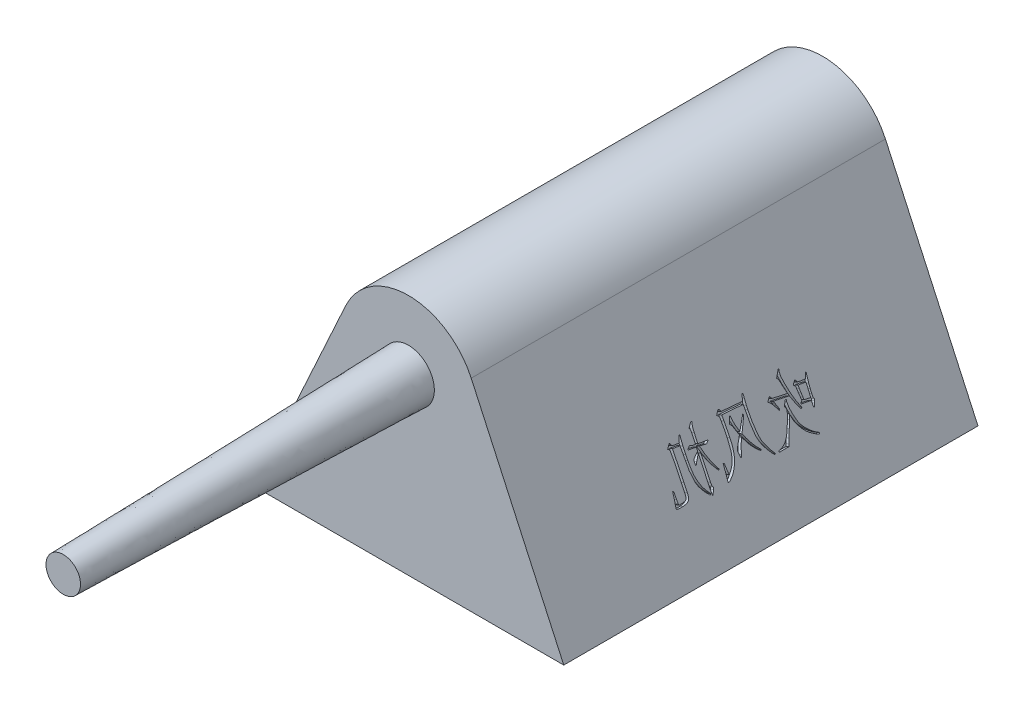
SolidWorks part; units mm, degrees
ref_plane "前视基准面" through (0, 0, 0) normal (0, 0, 1) x (1, 0, 0)
ref_plane "上视基准面" through (0, 0, 0) normal (0, 1, 0) x (1, 0, 0)
ref_plane "右视基准面" through (0, 0, 0) normal (1, 0, 0) x (0, 0, -1)
other "Configuration Table"
sketch "草图1" plane through (0, 0, 0) normal (0, 0, 1) x (1, 0, 0)
  line L1 (-60, 120) -> (60, 120)
  line L2 (-60, 120) -> (-60, 0)
  line L3 (-60, 0) -> (60, 0)
  line L4 (60, 120) -> (60, 0)
  dimension "D1" = 60
  dimension "D2" = 60
  dimension "D3" = 120
extrude "凸台-拉伸1" add sketch "草图1" along normal mid plane 120
ref_plane "基准面1" through (0, 0, 160) normal (0, 0, 1) x (1, 0, 0)
sketch "草图3" plane through (0, 0, 160) normal (0, 0, 1) x (1, 0, 0)
  line L0 (-60, 120) -> (60, 0) construction
  line L1 (60, 120) -> (-60, 0) construction
  line L2 (0, 0) -> (0, 100.1659) construction
  line L3 (-60, 0) -> (60, 0) construction
  circle A0 centre (0, 50.25) radius 5
  dimension "D1" = 10
  dimension "D2" = 50.25
sketch "草图4" plane through (0, 0, 60) normal (0, 0, 1) x (1, 0, 0)
  line L2 (0, 0) -> (0, 120) construction
  line L3 (-60, 0) -> (60, 0) construction
  line L4 (60, 120) -> (-60, 120) construction
  circle A0 centre (0, 50.25) radius 7.5
  point P8 (0, 0)
  dimension "D1" = 15
  dimension "D2" = 50.25
loft "放样1" add profiles "草图4", "草图3" connector at (4.5744, 56.1934, 60) connector at (1.4702, 55.029, 160)
sketch "草图5" plane through (0, 0, 60) normal (0, 0, 1) x (1, 0, 0)
  line L0 (-45, 0) -> (-18.185, 58.5749)
  line L1 (-60, 0) -> (60, 0) construction
  line L2 (18.185, 58.5749) -> (45, 0)
  line L3 (60, 0) -> (60, 120) construction
  line L4 (-60, 120) -> (-60, 0) construction
  line L5 (-45, 0) -> (-60, 0)
  line L6 (-60, 0) -> (-60, 120)
  line L7 (-60, 120) -> (60, 120)
  line L8 (60, 120) -> (60, 0)
  line L9 (60, 0) -> (45, 0)
  arc A0 (18.185, 58.5749) -> (-18.185, 58.5749) centre (0, 50.25) ccw
  point P1 (0, 0)
  point P2 (0, 0)
  point P21 (0, 50.25)
  point P22 (0, 0)
  point P23 (0, 0)
  dimension "D3" = 40
  dimension "D1" = 15
  dimension "D2" = 15
extrude "切除-拉伸1" cut sketch "草图5" against normal through all both and the other way through all
sketch "草图6" plane through (-37.2033, 17.0313, 0) normal (-0.9093, 0.4162, 0) x (0, 0, 1)
  line L0 (-60, 0) -> (60, 0) construction
  line L1 (-60, -18.7311) -> (-60, 45.6899) construction
  line L2 (60, -18.7311) -> (60, 45.6899) construction
  text T0 "     吹风机" font "汉仪长仿宋体" height in points 42
extrude "切除-拉伸2" cut sketch "草图6" against normal blind 1 and the other way through all
mirror "镜向1" about plane through (0, 0, 0) normal (1, 0, 0) of "切除-拉伸2"
